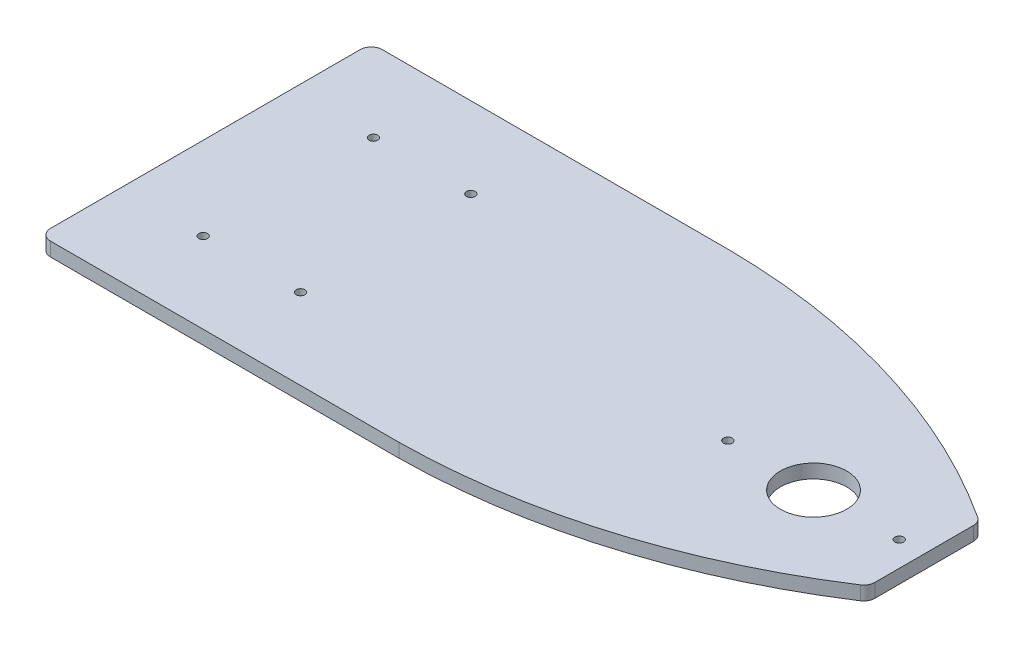
SolidWorks part; units mm, degrees
material "PLA"
ref_plane "Front" through (0, 0, 0) normal (0, 0, 1) x (1, 0, 0)
ref_plane "Top" through (0, 0, 0) normal (0, 1, 0) x (1, 0, 0)
ref_plane "Right" through (0, 0, 0) normal (1, 0, 0) x (0, 0, -1)
sketch "Sketch1" plane through (0, 0, 0) normal (0, 1, 0) x (1, 0, 0)
  line L1 (82.55, -38.1) -> (-82.55, -38.1)
  line L2 (82.55, -38.1) -> (82.55, 38.1)
  line L3 (82.55, 38.1) -> (-82.55, 38.1)
  line L4 (-82.55, -38.1) -> (-82.55, 38.1)
  line L5 (82.55, -38.1) -> (-82.55, 38.1) construction
  line L6 (82.55, 38.1) -> (-82.55, -38.1) construction
  point P0 (0, 0)
  dimension "D1" = 76.2
  dimension "D2" = 165.1
extrude "Boss-Extrude1" add sketch "Sketch1" along normal blind 3.175
sketch "Sketch4" plane through (0, 3.175, 0) normal (0, 1, 0) x (1, 0, 0)
  line L1 (82.55, -38.1) -> (0, -38.1)
  line L2 (82.55, 38.1) -> (82.55, 12.7)
  line L3 (82.55, -38.1) -> (82.55, 38.1) construction
  line L4 (82.55, -38.1) -> (82.55, -12.7)
  line L7 (82.55, 38.1) -> (0, 38.1)
  line L8 (0, -1.7463) -> (0, 1.7463) construction
  line L9 (-82.55, -38.1) -> (82.55, -38.1) construction
  arc A1 (0, 38.1) -> (82.55, 12.7) centre (-1.7067, -114.2904) cw
  arc A2 (0, -38.1) -> (82.55, -12.7) centre (-1.7067, 114.2904) ccw
  dimension "D3" = 152.4
  dimension "D4" = 152.4
  dimension "D1" = 25.4
  dimension "D2" = 25.4
extrude "Cut-Extrude1" cut sketch "Sketch4" against normal blind 3.175
fillet "Fillet3" radius 2.54 2 edges at (-82.55, 1.5875, 38.1) (-82.55, 1.5875, -38.1)
sketch "Sketch5" plane through (0, 3.175, 0) normal (0, 1, 0) x (1, 0, 0)
  line L0 (-1.7463, 0) -> (1.7463, 0) construction
  line L1 (82.55, -12.7) -> (82.55, 12.7) construction
  circle A0 centre (57.15, 0) radius 7.62
  dimension "D1" = 15.24
  dimension "D2" = 25.4
extrude "Cut-Extrude2" cut sketch "Sketch5" against normal blind 3.175
sketch "Sketch6" plane through (0, 3.175, 0) normal (0, 1, 0) x (1, 0, 0)
  line L1 (-63.5, 19.558) -> (-63.5, 0)
  line L2 (-63.5, -19.558) -> (-40.128, -19.558)
  line L4 (-24.13, 17.526) -> (-24.13, 16.5227)
  line L5 (-1.7463, 0) -> (1.7463, 0) construction
  line L6 (-63.5, 0) -> (-63.5, -19.558)
  line L7 (-43.815, -19.558) -> (-40.128, -19.558)
  circle A5 centre (-63.5, 19.558) radius 1.0033
  circle A8 centre (-63.5, -19.558) radius 1.0033
  circle A11 centre (-41.1313, -19.558) radius 1.0033
  circle A12 centre (-41.1313, 19.558) radius 1.0033
  dimension "D1" = 19.558
  dimension "D2" = 2.0066
  dimension "D8" = 2.0066
  dimension "D6" = 2.0066
  dimension "D3" = 19.558
sketch "Sketch7" plane through (0, 3.175, 0) normal (0, 1, 0) x (1, 0, 0)
  line L0 (57.15, -7.62) -> (57.15, 7.62)
  line L1 (57.15, 0) -> (76.835, 0)
  line L2 (-1.7463, 0) -> (1.7463, 0) construction
  line L3 (57.15, 0) -> (37.465, 0)
  circle A0 centre (57.15, 0) radius 7.62 construction
  circle A1 centre (76.835, 0) radius 1.0033
  circle A2 centre (37.465, 0) radius 1.0033
  dimension "D3" = 2.0066
  dimension "D4" = 2.0066
  dimension "D1" = 19.685
  dimension "D2" = 19.685
extrude "Cut-Extrude4" cut sketch "Sketch7" against normal through all contours A2 | A1 region at (36.4901, 3.175, 0)
extrude "Cut-Extrude5" cut sketch "Sketch6" against normal through all contours A5 | A8 | L2 A8 L6 | L4 L7 | L7 A11 | L7 A11 | A12 region at (-41.1313, 3.175, 19.1322) region at (-41.1313, 3.175, 19.9838) region at (-63.0742, 3.175, 19.1322) region at (-63.6419, 3.175, 19.6999) region at (-64.1894, 3.175, -20.2474) region at (-41.1313, 3.175, -19.558)
fillet "Fillet4" radius 2.54 2 edges at (82.55, 1.5875, 12.7) (82.55, 1.5875, -12.7)
